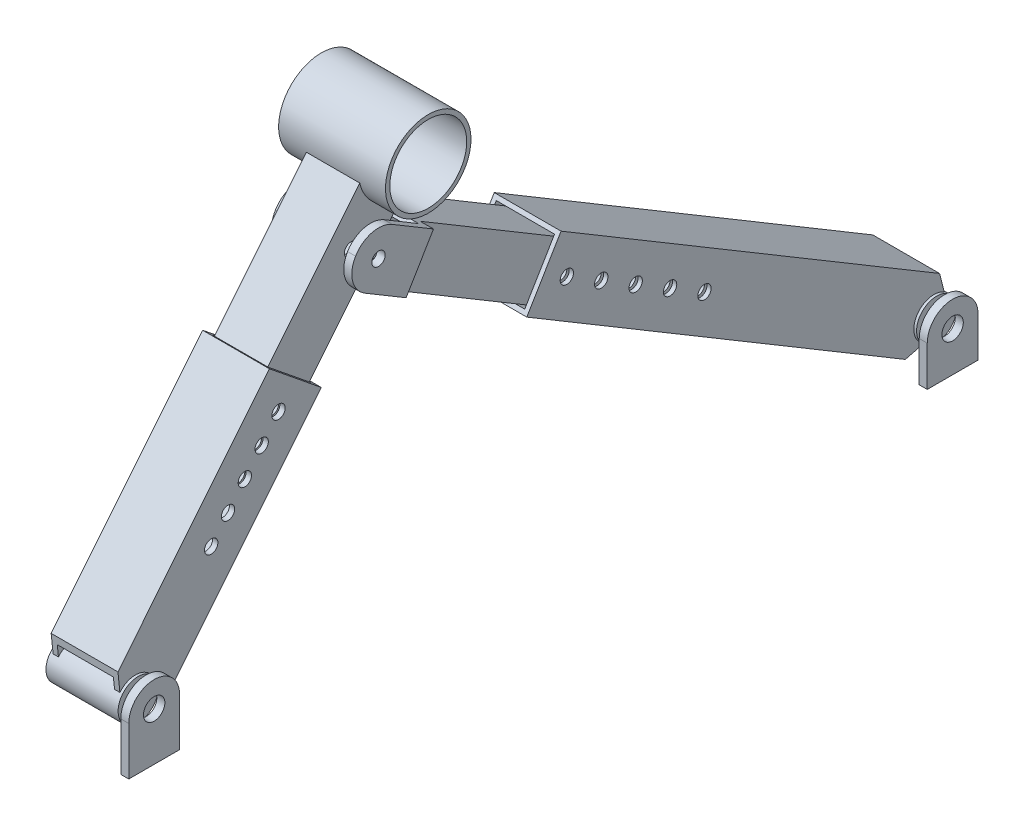
SolidWorks part; units mm, degrees
other "Pedal_Front2"
other "Pedal_Front1"
other "Pedal_Joint"
other "Pedal_Rear2"
other "Pedal_Rear1"
other "Support 2"
other "Support 1"
ref_plane "Front Plane" through (0, 0, 0) normal (0, 0, 1) x (1, 0, 0)
ref_plane "Top Plane" through (0, 0, 0) normal (0, 1, 0) x (1, 0, 0)
ref_plane "Right Plane" through (0, 0, 0) normal (1, 0, 0) x (0, 0, -1)
sketch "Sketch3" plane through (0, 0, 0) normal (1, 0, 0) x (0, 0, -1)
  line L0 (0, 0) -> (83.1885, 102.5659) construction
  line L1 (83.1885, 102.5659) -> (298.8584, -26.1467) construction
  line L2 (298.8584, -26.1467) -> (0, 0) construction
  line L3 (0, 0) -> (30.9997, 0) construction
  point P2 (0, 0)
  point P3 (0, 0)
  point P5 (0, 0)
  point P6 (36.5922, 39.3066)
  point P7 (72.4707, -6.3404)
  point P10 (207.2175, 90.1507)
  point P11 (118.9194, 149.585)
  point P12 (0, 0)
  point P13 (0, 0)
  point P14 (102.1344, 151.4736)
  point P15 (123.066, 154.0498)
  point P16 (161.4336, 141.5943)
  point P17 (123.9359, 179.4601)
  point P18 (126.7562, 140.1483)
  point P19 (137.859, 133.5441)
  point P20 (123.2141, 146.6901)
  point P21 (126.1565, 137.1002)
  point P22 (110.8056, 124.9757)
  point P23 (97.6911, 112.5805)
  point P24 (83.1885, 102.5659)
  point P25 (0, 0)
  point P26 (0, 0)
  dimension "D1" = 5
  dimension "D2" = 300
ref_plane "Plane1" through (0, 0, 0) normal (0, 0.7767, -0.6299) x (-1, 0, 0)
ref_plane "Plane2" through (0, -26.1467, -298.8584) normal (0, -0.5125, -0.8587) x (-1, 0, 0)
sketch "Sketch4" plane through (0, 0, 0) normal (0, 0.7767, -0.6299) x (-1, 0, 0)
  line L0 (-10.5, 10.5) -> (10.5, 10.5)
  line L1 (-12.5, -12.5) -> (12.5, -12.5)
  line L2 (-12.5, -12.5) -> (-12.5, 12.5)
  line L3 (-12.5, 12.5) -> (12.5, 12.5)
  line L4 (12.5, -12.5) -> (12.5, 12.5)
  line L5 (-12.5, -12.5) -> (12.5, 12.5) construction
  line L6 (-12.5, 12.5) -> (12.5, -12.5) construction
  line L7 (10.5, -10.5) -> (10.5, 10.5)
  line L8 (-10.5, -10.5) -> (10.5, -10.5)
  line L9 (-10.5, -10.5) -> (-10.5, 10.5)
  point P0 (0, 0)
  dimension "D1" = 25
  dimension "D2" = 2
extrude "Boss-Extrude3" add sketch "Sketch4" along normal blind 95 separate body
sketch "Sketch9" plane through (0, -26.1467, -298.8584) normal (0, -0.5125, -0.8587) x (-1, 0, 0)
  line L0 (10.9, 10.9) -> (-10.9, 10.9)
  line L1 (12.5, -12.5) -> (-12.5, -12.5)
  line L2 (12.5, -12.5) -> (12.5, 12.5)
  line L3 (12.5, 12.5) -> (-12.5, 12.5)
  line L4 (-12.5, -12.5) -> (-12.5, 12.5)
  line L5 (12.5, -12.5) -> (-12.5, 12.5) construction
  line L6 (12.5, 12.5) -> (-12.5, -12.5) construction
  line L7 (-10.9, -10.9) -> (-10.9, 10.9)
  line L8 (10.9, -10.9) -> (-10.9, -10.9)
  line L9 (10.9, -10.9) -> (10.9, 10.9)
  point P0 (0, 0)
  dimension "D1" = 1.6
  dimension "D2" = 25
extrude "Boss-Extrude6" add sketch "Sketch9" against normal blind 170
sketch "Sketch7" plane through (0, 0, 0) normal (1, 0, 0) x (0, 0, -1)
  line L0 (305.2644, -15.413) -> (292.4525, -36.8805) construction
  circle A0 centre (0, 0) radius 7.5
  circle A1 centre (298.8584, -26.1467) radius 7.5
  dimension "D1" = 15
  dimension "D2" = 285
extrude "Cut-Extrude2" cut sketch "Sketch7" against normal mid plane 170 contours A0 | A1
sketch "Sketch2" plane through (0, 0, 0) normal (1, 0, 0) x (0, 0, -1)
  circle A0 centre (0, 0) radius 4
  circle A1 centre (0, 0) radius 7.5
  circle A2 centre (298.8584, -26.1467) radius 4
  circle A3 centre (298.8584, -26.1467) radius 7.5
  arc A5 (5.8249, -4.7244) -> (-5.8249, 4.7244) centre (0, 0) ccw construction
  dimension "D1" = 8
extrude "Boss-Extrude2" add sketch "Sketch2" along normal mid plane 27
sketch "Sketch5" plane through (0, 0, 0) normal (0, 0.7767, -0.6299) x (-1, 0, 0)
  line L0 (-8, -8) -> (-8, 8)
  line L1 (-10, -10) -> (10, -10)
  line L2 (-10, -10) -> (-10, 10)
  line L3 (-10, 10) -> (10, 10)
  line L4 (10, -10) -> (10, 10)
  line L5 (-10, -10) -> (10, 10) construction
  line L6 (-10, 10) -> (10, -10) construction
  line L7 (-8, 8) -> (8, 8)
  line L8 (8, -8) -> (8, 8)
  line L9 (-8, -8) -> (8, -8)
  point P0 (0, 0)
  dimension "D1" = 20
  dimension "D2" = 2
extrude "Boss-Extrude4" add sketch "Sketch5" along normal up to vertex (132.0609 mm away) from offset 60 separate body
sketch "Sketch10" plane through (0, -26.1467, -298.8584) normal (0, -0.5125, -0.8587) x (-1, 0, 0)
  line L1 (8, -8) -> (8, 8)
  line L2 (10, -10) -> (-10, -10)
  line L3 (10, -10) -> (10, 10)
  line L4 (10, 10) -> (-10, 10)
  line L5 (-10, -10) -> (-10, 10)
  line L6 (10, -10) -> (-10, 10) construction
  line L7 (10, 10) -> (-10, -10) construction
  line L8 (8, 8) -> (-8, 8)
  line L9 (-8, -8) -> (-8, 8)
  line L10 (8, -8) -> (-8, -8)
  point P0 (-39.7297, 20.8928)
  point P2 (0, 0)
  dimension "D1" = 20
  dimension "D2" = 2
extrude "Boss-Extrude7" add sketch "Sketch10" against normal blind 160 from offset 70 separate body offset against normal yes
sketch "Sketch17" plane through (0, 102.5659, -83.1885) normal (0, 0.7767, -0.6299) x (1, 0, 0)
  line L0 (8, 8) -> (-8, 8) construction
  line L1 (-8, 8) -> (-8, -8) construction
  line L2 (-8, -8) -> (8, -8) construction
  line L3 (8, -8) -> (8, 8) construction
  line L4 (-10, 10) -> (-10, -10)
  line L5 (-10, -10) -> (10, -10)
  line L6 (10, -10) -> (10, 10)
  line L7 (10, 10) -> (-10, 10)
  line L8 (-10, 10) -> (-10, -10)
  line L9 (-10, -10) -> (10, -10)
  line L10 (10, -10) -> (10, 10)
  line L11 (10, 10) -> (-10, 10)
  line L12 (-8, -8) -> (8, -8)
  line L13 (8, -8) -> (8, 8)
  line L14 (-8, 8) -> (-8, -8)
  line L15 (8, 8) -> (-8, 8)
  dimension "D1" = 0
extrude "Boss-Extrude11" add sketch "Sketch17" along normal blind 30
sketch "Sketch11" plane through (0, 0, 0) normal (1, 0, 0) x (0, 0, -1)
  line L0 (83.1885, 102.5659) -> (102.0862, 125.8655) construction
  line L1 (0, 0) -> (83.1885, 102.5659) construction
  circle A0 centre (102.0862, 125.8655) radius 16
  dimension "D1" = 32
  dimension "D2" = 30
extrude "Cut-Extrude3" cut sketch "Sketch11" against normal mid plane 25
sketch "Sketch12" plane through (0, 0, 0) normal (1, 0, 0) x (0, 0, -1)
  line L0 (83.1885, 102.5659) -> (102.0862, 125.8655) construction
  line L1 (0, 0) -> (83.1885, 102.5659) construction
  circle A0 centre (102.0862, 125.8655) radius 16
  circle A3 centre (102.0862, 125.8655) radius 14.4
  point P9 (0, 0)
  dimension "D1" = 32
  dimension "D3" = 30
  dimension "D2" = 1.6
extrude "Boss-Extrude8" add sketch "Sketch12" along normal mid plane 40
chamfer "Chamfer1" distance 5 angle 45 2 edges at (0, -7.8741, -9.7082) (0, 7.8741, 9.7082)
chamfer "Chamfer2" distance 5 angle 45 2 edges at (0, -15.413, -305.2644) (0, -36.8805, -292.4525)
sketch "Sketch13" plane through (0, 0, 0) normal (1, 0, 0) x (0, 0, -1)
  line L0 (0, 0) -> (83.1885, 102.5659) construction
  line L1 (67.9978, 67.1681) -> (51.688, 80.3965) construction
  circle A0 centre (53.5436, 66.0157) radius 2.5
  point P14 (0, 0)
  dimension "D1" = 5
  dimension "D2" = 10
extrude "Cut-Extrude4" cut sketch "Sketch13" against normal mid plane 40
sketch "Sketch15" plane through (0, 0, 0) normal (1, 0, 0) x (0, 0, -1)
  line L0 (83.1885, 102.5659) -> (298.8584, -26.1467) construction
  line L1 (147.2932, 51.6144) -> (158.4651, 70.3341) construction
  circle A0 centre (161.4662, 55.8495) radius 2.5
  circle A1 centre (53.5436, 66.0157) radius 2.5 construction
  point P6 (186.2585, 89.2741)
  dimension "D1" = 10
extrude "Cut-Extrude5" cut sketch "Sketch15" against normal mid plane 40
pattern_linear "LPattern1" count 5 spacing 10 along (0, -0.7767, 0.6299) of "Cut-Extrude4"
pattern_linear "LPattern2" count 5 spacing 15 along (0, -0.5125, -0.8587) of "Cut-Extrude5"
sketch "Sketch16" plane through (0, 0, 0) normal (1, 0, 0) x (0, 0, -1)
  line L0 (-9.5, 0) -> (-9.5, -18)
  line L1 (-9.5, -18) -> (9.5, -18)
  line L2 (9.5, -18) -> (9.5, 0)
  line L3 (289.3584, -26.1467) -> (289.3584, -41.1467)
  line L4 (289.3584, -41.1467) -> (308.3584, -41.1467)
  line L5 (308.3584, -41.1467) -> (308.3584, -26.1467)
  circle A0 centre (0, 0) radius 4
  circle A1 centre (0, 0) radius 4 construction
  arc A2 (9.5, 0) -> (-9.5, 0) centre (0, 0) ccw
  arc A3 (5.8249, -4.7244) -> (-5.8249, 4.7244) centre (0, 0) ccw construction
  circle A4 centre (298.8584, -26.1467) radius 4 construction
  circle A5 centre (298.8584, -26.1467) radius 4
  arc A6 (308.3584, -26.1467) -> (289.3584, -26.1467) centre (298.8584, -26.1467) ccw
  circle A7 centre (298.8584, -26.1467) radius 7.5 construction
  dimension "D1" = 2
  dimension "D3" = 2
  dimension "D2" = 18
  dimension "D4" = 15
extrude "Boss-Extrude10" add sketch "Sketch16" along normal mid plane 3 from offset 18
sketch "Sketch18" plane through (0, -20.5143, -34.3736) normal (0, 0.5125, 0.8587) x (1, 0, 0)
  line L0 (-10, 140.7056) -> (-15, 140.7056)
  line L1 (-10, 120.7056) -> (-15, 120.7056)
  line L2 (-15, 120.7056) -> (-15, 140.7056)
  line L3 (10, 140.7056) -> (15, 140.7056)
  line L4 (15, 140.7056) -> (15, 120.7056)
  line L5 (15, 120.7056) -> (10, 120.7056)
  line L6 (-10, 120.7056) -> (-10, 140.7056)
  line L7 (10, 120.7056) -> (10, 140.7056)
  dimension "D1" = 5
extrude "Boss-Extrude12" add sketch "Sketch18" against normal blind 3
sketch "Sketch19" plane through (0, -20.5143, -34.3736) normal (0, 0.5125, 0.8587) x (1, 0, 0)
  line L0 (15, 120.7056) -> (-15, 120.7056) construction
  line L1 (-15, 140.7056) -> (-12, 140.7056)
  line L2 (-15, 140.7056) -> (-15, 120.7056)
  line L3 (-15, 120.7056) -> (-12, 120.7056)
  line L4 (-12, 140.7056) -> (-12, 120.7056)
  line L6 (15, 140.7056) -> (12, 140.7056)
  line L7 (15, 140.7056) -> (15, 120.7056)
  line L8 (15, 120.7056) -> (12, 120.7056)
  line L9 (12, 140.7056) -> (12, 120.7056)
  dimension "D1" = 3
extrude "Boss-Extrude13" add sketch "Sketch19" along normal blind 25
fillet "Fillet1" radius 10 4 edges at (-13.5, 95.9477, -74.7648) (-13.5, 113.1217, -85.0143) (13.5, 113.1217, -85.0143) (13.5, 95.9477, -74.7648)
sketch "Sketch20" plane through (10, 0, 0) normal (1, 0, 0) x (0, 0, -1)
  circle A0 centre (83.1885, 102.5659) radius 2.5
  dimension "D1" = 5
extrude "Cut-Extrude6" cut sketch "Sketch20" against normal blind 25
sketch "Sketch21" plane through (15, 0, 0) normal (1, 0, 0) x (0, 0, -1)
  line L0 (83.1885, 102.5659) -> (298.8584, -26.1467) construction
  circle A0 centre (88.4765, 99.4099) radius 2.5
  arc A1 (93.6013, 107.9969) -> (79.8895, 104.5347) centre (88.4765, 99.4099) ccw construction
  arc A2 (79.8895, 104.5347) -> (83.3518, 90.8229) centre (88.4765, 99.4099) ccw construction
  point P8 (88.4765, 99.4099)
  dimension "D1" = 5
extrude "Cut-Extrude7" cut sketch "Sketch21" against normal blind 40
other "Save Bodies1"
